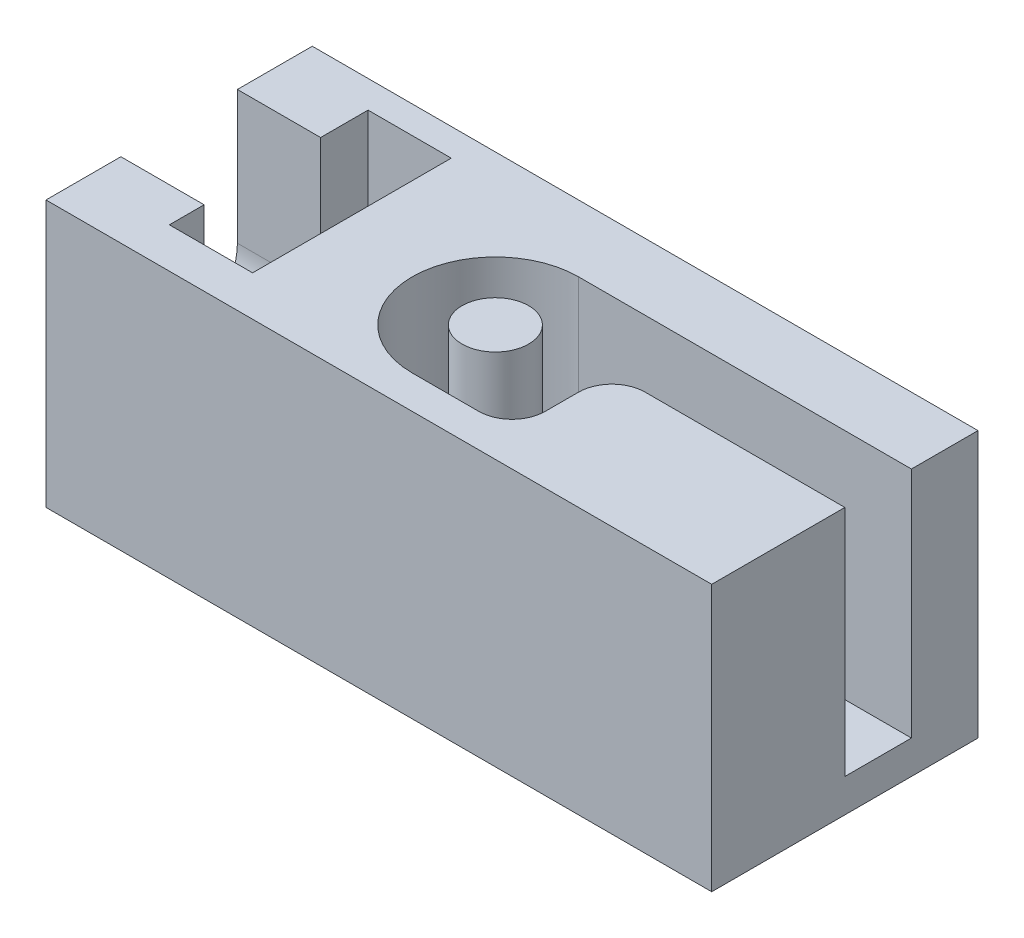
SolidWorks part; units mm, degrees
ref_plane "Front Plane" through (0, 0, 0) normal (0, 0, 1) x (1, 0, 0)
ref_plane "Top Plane" through (0, 0, 0) normal (0, 1, 0) x (1, 0, 0)
ref_plane "Right Plane" through (0, 0, 0) normal (1, 0, 0) x (0, 0, -1)
sketch "Sketch1" plane through (0, 0, 0) normal (0, 1, 0) x (1, 0, 0)
  line L1 (0, 0) -> (20, 0)
  line L2 (0, 0) -> (0, 8)
  line L3 (0, 8) -> (20, 8)
  line L4 (20, 0) -> (20, 8)
  dimension "D1" = 8
  dimension "D2" = 20
extrude "Boss-Extrude1" add sketch "Sketch1" along normal blind 8
sketch "Sketch2" plane through (0, 8, 0) normal (0, 1, 0) x (1, 0, 0)
  line L0 (20, 6) -> (10, 6)
  line L1 (20, 0) -> (20, 8) construction
  line L2 (10, 1) -> (12, 1)
  line L3 (13, 2) -> (13, 3)
  line L4 (14, 4) -> (20, 4)
  line L5 (20, 4) -> (20, 6)
  line L6 (0, 0) -> (20, 0) construction
  arc A0 (10, 6) -> (10, 1) centre (10, 3.5) ccw
  circle A1 centre (10, 3.5) radius 1
  arc A2 (13, 3) -> (14, 4) centre (14, 3) cw
  arc A3 (12, 1) -> (13, 2) centre (12, 2) ccw
  point P16 (13, 1)
  dimension "D4" = 2.5
  dimension "D6" = 1.5
  dimension "D7" = 1
  dimension "D1" = 6
  dimension "D2" = 10
  dimension "D3" = 2
  dimension "D5" = 3
extrude "Cut-Extrude1" cut sketch "Sketch2" against normal blind 7
sketch "Sketch4" plane through (0, 0, 0) normal (-1, 0, 0) x (0, 0, 1)
  line L0 (-8, 0) -> (0, 8) construction
  line L1 (-5.75, 4) -> (-5.75, 8)
  line L2 (-8, 8) -> (0, 8) construction
  line L3 (-5.75, 8) -> (-2.25, 8)
  line L4 (-2.25, 8) -> (-2.25, 4)
  arc A0 (-5.75, 4) -> (-2.25, 4) centre (-4, 4) ccw
  dimension "D1" = 3.5
extrude "Cut-Extrude2" cut sketch "Sketch4" against normal blind 5
sketch "Sketch5" plane through (5, 0, 0) normal (-1, 0, 0) x (0, 0, 1)
  line L0 (-7.1754, 3.5) -> (-7.1754, 14.0662)
  line L1 (-7.1754, 3.5) -> (-5.079, 1.0135)
  line L2 (-5.079, 1.0135) -> (-1.9532, 1.5723)
  line L3 (-1.9532, 1.5723) -> (-1.2068, 3.6381)
  line L7 (-1.2068, 3.6381) -> (-1.2068, 14.0662)
  line L8 (-1.2068, 14.0662) -> (-7.1754, 14.0662)
  line L9 (-6.0468, 6.4277) -> (-6.5864, 4.9345) [skipped]
  line L10 (-2.921, 6.9865) -> (-4.4839, 6.7071) [skipped]
  line L11 (-0.8741, 4.5588) -> (-1.8975, 5.7726) [skipped]
  circle A0 centre (-4, 4) radius 2.75 construction
  dimension "D1" = 5.5
extrude "Cut-Extrude3" cut sketch "Sketch5" along normal blind 2.5
